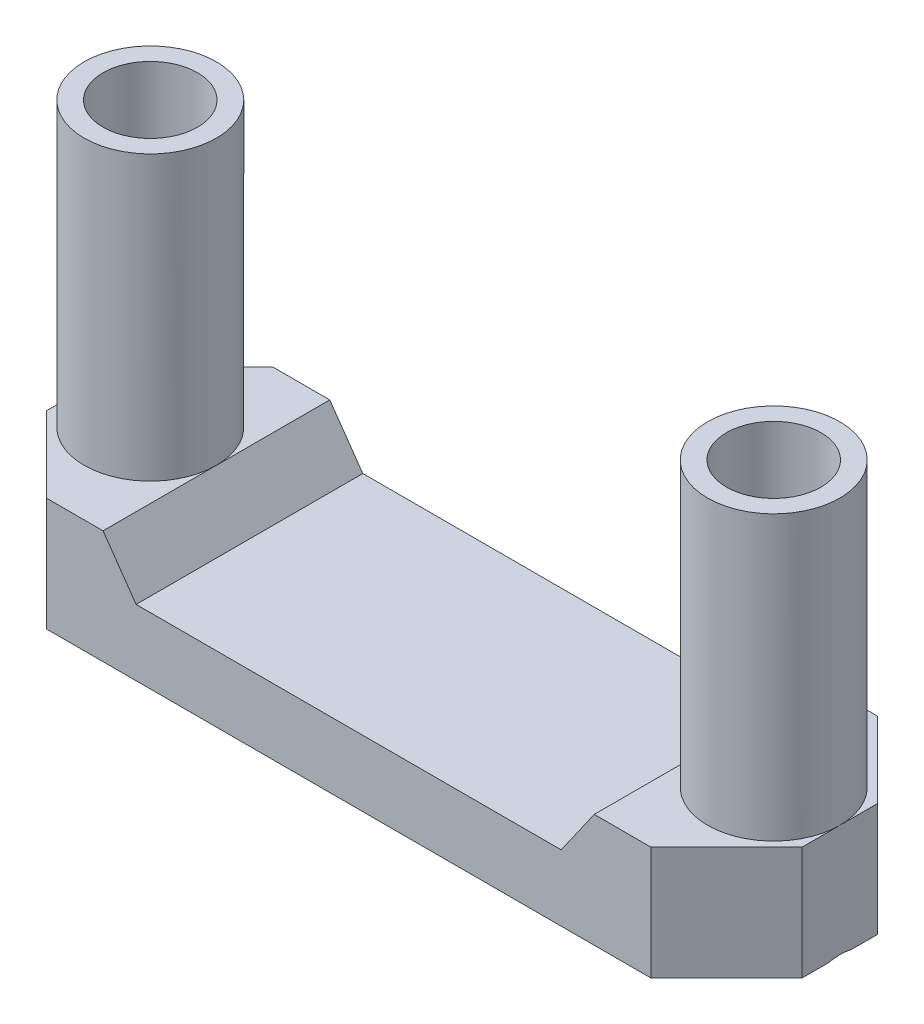
SolidWorks part; units mm, degrees
ref_plane "Front Plane" through (0, 0, 0) normal (0, 0, 1) x (1, 0, 0)
ref_plane "Top Plane" through (0, 0, 0) normal (0, 1, 0) x (1, 0, 0)
ref_plane "Right Plane" through (0, 0, 0) normal (1, 0, 0) x (0, 0, -1)
sketch "Sketch1" plane through (0, 0, 0) normal (0, 1, 0) x (1, 0, 0)
  line L0 (-10, 0) -> (10, 0) construction
  line L1 (-10, -3) -> (10, -3)
  line L2 (-10, -3) -> (-10, 3)
  line L3 (-10, 3) -> (10, 3)
  line L4 (10, -3) -> (10, 3)
  line L5 (-10, -3) -> (10, 3) construction
  line L6 (-10, 3) -> (10, -3) construction
  line L7 (0, -3) -> (0, 3) construction
  line L8 (-9.5, -3) -> (-9.5, 3) construction
  circle A0 centre (-8.25, 0) radius 1.25
  circle A2 centre (8.25, 0) radius 1.25
  point P0 (0, 0)
  dimension "D4" = 2.5
  dimension "D1" = 6
  dimension "D2" = 20
  dimension "D3" = 0.5
extrude "Boss-Extrude1" add sketch "Sketch1" along normal blind 3
sketch "Sketch2" plane through (0, 3, 0) normal (0, 1, 0) x (1, 0, 0)
  line L0 (10, 3) -> (-10, 3) construction
  line L1 (-6.5, -3) -> (6.5, -3)
  line L2 (-6.5, -3) -> (-6.5, 3)
  line L3 (-6.5, 3) -> (6.5, 3)
  line L4 (6.5, -3) -> (6.5, 3)
  line L5 (-6.5, -3) -> (6.5, 3) construction
  line L6 (-6.5, 3) -> (6.5, -3) construction
  point P0 (0, 0)
  dimension "D1" = 13
extrude "Cut-Extrude1" cut sketch "Sketch2" against normal blind 1.25
chamfer "Chamfer1" distance 2 angle 45 4 edges at (10, 1.5, -3) (10, 1.5, 3) (-10, 1.5, -3) (-10, 1.5, 3)
sketch "Sketch3" plane through (0, 3, 0) normal (0, 1, 0) x (1, 0, 0)
  circle A0 centre (-8.25, 0) radius 1.25
  circle A1 centre (-8.25, 0) radius 1.75
  dimension "D1" = 0.5
extrude "Boss-Extrude2" add sketch "Sketch3" along normal blind 7.5
mirror "Mirror1" about plane through (0, 0, 0) normal (1, 0, 0) of "Boss-Extrude2"
fillet "Fillet1" [suppressed] radius 0.5
chamfer "Chamfer2" distance 0.75 angle 35 2 edges at (8.25, 0, -1.25) (-8.25, 0, 1.25) first distance on face at (8.25, 0, -1.25) first distance on face at (-8.25, 0, 1.25)
chamfer "Chamfer3" distance 1.25 angle 35 2 edges at (6.5, 1.75, 0) (-6.5, 1.75, 0) first distance on face at (6.5, 2.5, 0) first distance on face at (-6.5, 2.5, 0)
